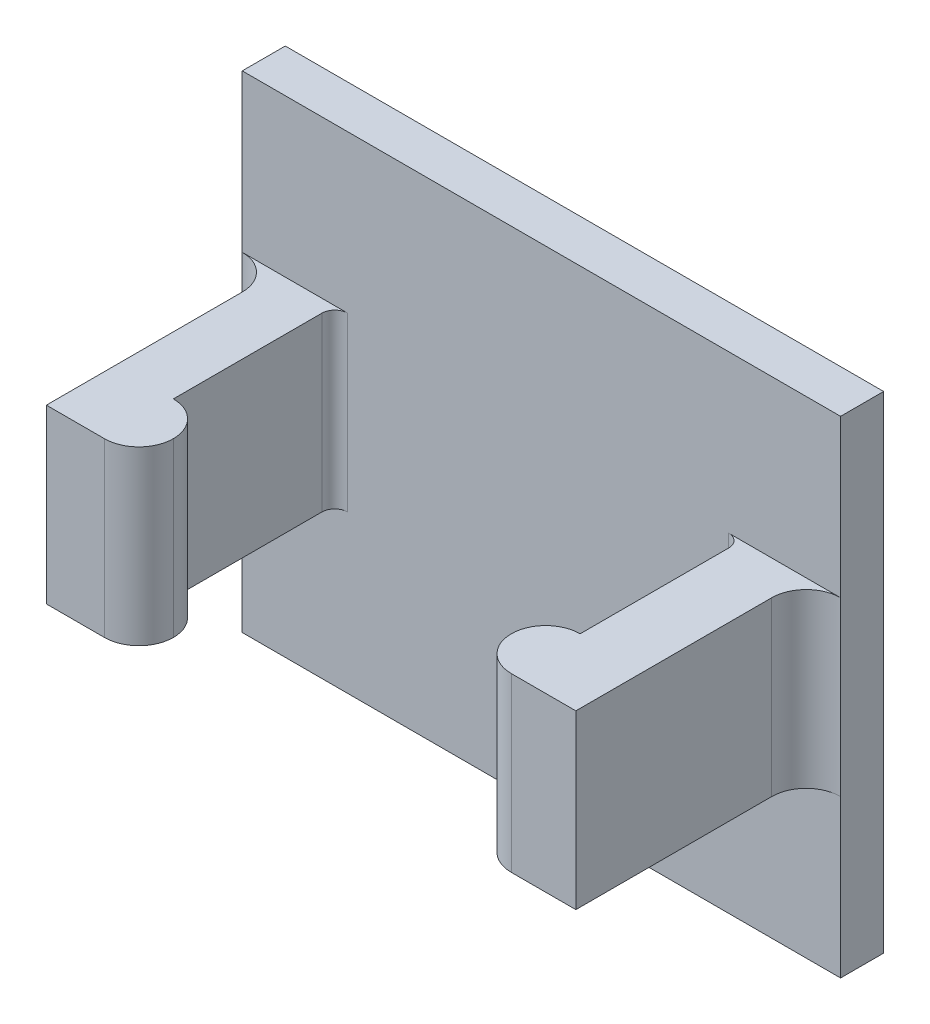
SolidWorks part; units mm, degrees
ref_plane "정면" through (0, 0, 0) normal (0, 0, 1) x (1, 0, 0)
ref_plane "윗면" through (0, 0, 0) normal (0, 1, 0) x (1, 0, 0)
ref_plane "우측면" through (0, 0, 0) normal (1, 0, 0) x (0, 0, -1)
sketch "스케치1" plane through (0, 0, 0) normal (0, 0, 1) x (1, 0, 0)
  line L1 (-6.15, -5.65) -> (6.15, -5.65)
  line L2 (-6.15, -5.65) -> (-6.15, 5.65)
  line L3 (-6.15, 5.65) -> (6.15, 5.65)
  line L4 (6.15, -5.65) -> (6.15, 5.65)
  line L5 (-6.15, -5.65) -> (6.15, 5.65) construction
  line L6 (-6.15, 5.65) -> (6.15, -5.65) construction
  point P0 (0, 0)
  dimension "D1" = 12.3
  dimension "D2" = 11.3
extrude "보스-돌출1" add sketch "스케치1" along normal blind 1
sketch "스케치2" plane through (0, 0, 1) normal (0, 0, 1) x (1, 0, 0)
  line L0 (-6.15, 5.65) -> (-6.15, -5.65) construction
  line L1 (-6.15, 2) -> (-4.8, 2)
  line L2 (-6.15, 2) -> (-6.15, -2)
  line L3 (-6.15, -2) -> (-4.8, -2)
  line L4 (-4.8, 2) -> (-4.8, -2)
  line L5 (6.15, -5.65) -> (6.15, 5.65) construction
  line L6 (6.15, 2) -> (4.65, 2)
  line L7 (6.15, 2) -> (6.15, -2)
  line L8 (6.15, -2) -> (4.65, -2)
  line L9 (4.65, 2) -> (4.65, -2)
  point P12 (-4.8, 0)
  point P14 (6.15, 0)
  dimension "D1" = 1.35
  dimension "D2" = 1.5
  dimension "D3" = 4
  dimension "D4" = 4
  dimension "D5" = 0
  dimension "D6" = 0
extrude "보스-돌출2" add sketch "스케치2" along normal blind 5.35
sketch "스케치3" plane through (-4.8, 0, 0) normal (1, 0, 0) x (0, 0, -1)
  line L0 (-6.35, -2) -> (-1, -2) construction
  line L1 (-6.35, 2) -> (-4.75, 2)
  line L2 (-6.35, 2) -> (-6.35, -2)
  line L3 (-6.35, -2) -> (-4.75, -2)
  line L4 (-4.75, 2) -> (-4.75, -2)
  dimension "D1" = 1.6
extrude "보스-돌출3" add sketch "스케치3" along normal blind 0.8
sketch "스케치4" plane through (4.65, 0, 0) normal (-1, 0, 0) x (0, 0, 1)
  line L0 (6.35, -2) -> (1, -2) construction
  line L1 (6.35, 2) -> (4.75, 2)
  line L2 (6.35, 2) -> (6.35, -2)
  line L3 (6.35, -2) -> (4.75, -2)
  line L4 (4.75, 2) -> (4.75, -2)
  dimension "D1" = 1.6
extrude "보스-돌출4" add sketch "스케치4" along normal blind 0.8
fillet "필렛1" radius 0.8 4 edges at (3.85, 0, 6.35) (3.85, 0, 4.75) (-4, 0, 6.35) (-4, 0, 4.75)
fillet "필렛2" radius 0.3 2 edges at (4.65, 0, 1) (-4.8, 0, 1)
sketch "스케치5" plane through (-6.15, 0, 0) normal (-1, 0, 0) x (0, 0, 1)
  line L1 (0, 5.65) -> (1, 5.65)
  line L2 (0, 5.65) -> (0, -5.65)
  line L3 (0, -5.65) -> (1, -5.65)
  line L4 (1, 5.65) -> (1, -5.65)
extrude "보스-돌출5" add sketch "스케치5" along normal blind 0.8
sketch "스케치6" plane through (6.15, 0, 0) normal (1, 0, 0) x (0, 0, -1)
  line L1 (-1, 5.65) -> (0, 5.65)
  line L2 (-1, 5.65) -> (-1, -5.65)
  line L3 (-1, -5.65) -> (0, -5.65)
  line L4 (0, 5.65) -> (0, -5.65)
extrude "보스-돌출6" add sketch "스케치6" along normal blind 0.8
fillet "필렛3" radius 0.8 2 edges at (-6.15, 0, 1) (6.15, 0, 1)
